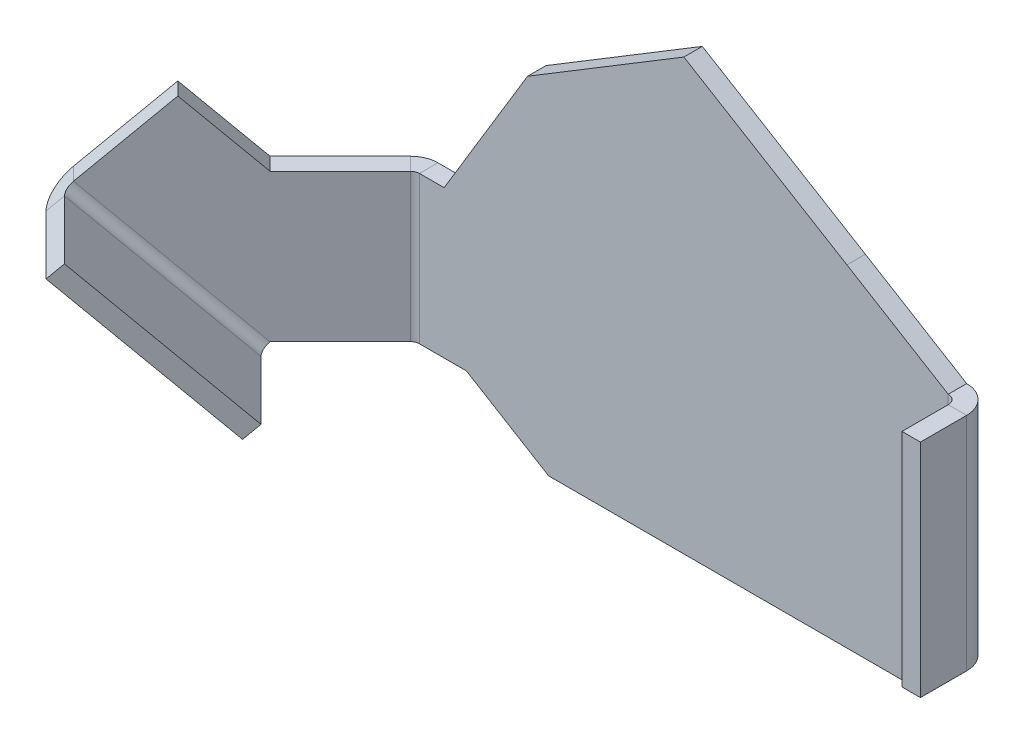
SolidWorks part; units mm, degrees
note: The reader was unsure of these and kept them because the rebuilt part matched: flange length of "Brida de arista1", "Brida de arista2", "Brida de arista3".
ref_plane "Alzado" through (0, 0, 0) normal (0, 0, 1) x (1, 0, 0)
ref_plane "Planta" through (0, 0, 0) normal (0, 1, 0) x (1, 0, 0)
ref_plane "Vista lateral" through (0, 0, 0) normal (1, 0, 0) x (0, 0, -1)
sketch "Croquis1" plane through (0, 0, 0) normal (0, 0, 1) x (1, 0, 0)
  line L1 (-21.5, -17.5) -> (21.5, -17.5)
  line L2 (-21.5, -17.5) -> (-21.5, 17.5)
  line L3 (-21.5, 17.5) -> (21.5, 17.5)
  line L4 (21.5, -17.5) -> (21.5, 17.5)
  line L5 (-21.5, -17.5) -> (21.5, 17.5) construction
  line L6 (-21.5, 17.5) -> (21.5, -17.5) construction
  point P0 (0, 0)
  dimension "D1" = 43
  dimension "D2" = 35
base flange "Brida base1" sketch "Croquis1" thickness 1.5 reverse thickness direction no parameters "D1"=0.7366
sketch "Croquis6" plane through (0, 0, 0) normal (0, 0, 1) x (1, 0, 0)
  line L0 (19.5, -17.5) -> (21.5, -13.5)
  line L1 (-21.5, -17.5) -> (21.5, -17.5) construction
  line L2 (21.5, -17.5) -> (21.5, 17.5) construction
  line L3 (19.5, -17.5) -> (-11, -17.5)
  line L4 (-21.5, -13.45) -> (-17.6841, -13.45)
  line L5 (-21.5, 17.5) -> (-21.5, -17.5) construction
  line L6 (21.5, -13.5) -> (21.5, 4.5)
  line L7 (-17.6841, -13.45) -> (-11, -17.5)
  line L8 (-21.5, -13.45) -> (-21.5, -1.45)
  line L9 (-21.5, -1.45) -> (-19.5, -1.45)
  line L10 (21.5, 4.5) -> (13.2608, 9.4923)
  line L11 (13.2608, 9.4923) -> (0, 17.5)
  line L12 (21.5, 17.5) -> (-21.5, 17.5) construction
  line L13 (-19.5, -1.45) -> (-12.7119, 9.7911)
  line L14 (-12.7119, 9.7911) -> (0, 17.5)
  line L16 (-29.7834, -22.9401) -> (29.7834, -22.9401)
  line L17 (-29.7834, -22.9401) -> (-29.7834, 22.9401)
  line L18 (-29.7834, 22.9401) -> (29.7834, 22.9401)
  line L19 (29.7834, -22.9401) -> (29.7834, 22.9401)
  line L20 (-29.7834, -22.9401) -> (29.7834, 22.9401) construction
  line L21 (-29.7834, 22.9401) -> (29.7834, -22.9401) construction
  point P12 (0, 0)
  dimension "D1" = 10.5
  dimension "D2" = 30.5
  dimension "D3" = 4
  dimension "D4" = 18
  dimension "D5" = 4.05
  dimension "D6" = 12
  dimension "D7" = 2
extrude "Cortar-Extruir1" cut sketch "Croquis6" against normal blind 10 normal cut yes
edge flange "Brida de arista1" sketch "Croquis9" flange angle 90 flange length 6 flange position bend outside bend radius 0.7366 thickness 1.5 relief rectangular parameters "D6"=10
sketch "Croquis9" plane through (21.5, 0, 0) normal (1, 0, 0) x (0, 1, 0)
  line L2 (-13.5, 0) -> (-13.5, 4.5)
  line L3 (-13.5, 4.5) -> (4.5, 4.5)
  line L4 (4.5, 4.5) -> (4.5, 0)
  line L5 (-13.5, 0) -> (4.5, 0) construction
  line L6 (-13.5, 0) -> (4.5, 0)
bend "Pliegue de arista1" bend radius 0.7366 bend angle 90 parameters "D5"=1
edge flange "Brida de arista2" sketch "Croquis12" flange angle 135 flange length 21 flange position bend outside bend radius 0.7366 thickness 1.5 relief rectangular parameters "D6"=10
sketch "Croquis12" plane through (-21.5, 0, 0) normal (-0.7071, 0, -0.7071) x (0, -1, 0)
  line L2 (1.45, 0) -> (1.45, 20.3787)
  line L3 (1.45, 20.3787) -> (13.45, 20.3787)
  line L4 (13.45, 20.3787) -> (13.45, 0)
  line L5 (1.45, 0) -> (13.45, 0) construction
  line L6 (1.45, 0) -> (13.45, 0)
bend "Pliegue de arista2" bend radius 0.7366 bend angle 45 parameters "D5"=2
sketch "Croquis13" plane through (-11.9632, 0, -11.9632) normal (-0.7071, 0, -0.7071) x (-0.7071, 0, 0.7071)
  line L0 (35.7972, -1.45) -> (21.5131, -15.7341)
  line L2 (35.7972, -13.45) -> (35.7972, -1.45) construction
  line L3 (35.7972, -1.45) -> (35.7972, -15.7341)
  line L4 (35.7972, -15.7341) -> (21.5131, -15.7341)
  dimension "D1" = 45
extrude "Cortar-Extruir2" cut sketch "Croquis13" against normal blind 10 normal cut yes
sketch "Croquis14" plane through (-11.9632, 0, -11.9632) normal (-0.7071, 0, -0.7071) x (-0.7071, 0, 0.7071)
  line L0 (23.7972, -1.45) -> (30.1612, 4.914)
  line L1 (35.7972, -1.45) -> (15.7237, -1.45) construction
  line L2 (30.1612, 4.914) -> (36.1612, -1.086)
  line L3 (35.7972, -1.45) -> (36.1612, -1.086)
  line L4 (23.7972, -1.45) -> (35.7972, -1.45)
  dimension "D1" = 135
  dimension "D2" = 12
  dimension "D3" = 9
extrude "Saliente-Extruir1" add sketch "Croquis14" against normal up to surface (1.5 mm away) up to face at (-26.9966, -7.45, 5.1915)
sketch "Croquis15" plane through (-11.9632, 0, -11.9632) normal (-0.7071, 0, -0.7071) x (-0.7071, 0, 0.7071)
  line L0 (30.1612, 4.914) -> (36.1612, -1.086)
  line L1 (36.1612, -1.086) -> (35.1005, -2.1467)
  line L2 (23.7972, -13.45) -> (36.1612, -1.086) construction
  line L3 (35.1005, -2.1467) -> (29.1005, 3.8533)
  line L4 (30.1612, 4.914) -> (23.7972, -1.45) construction
  line L5 (29.1005, 3.8533) -> (30.1612, 4.914)
  dimension "D1" = 1.5
extrude "Cortar-Extruir3" cut sketch "Croquis15" against normal blind 10 normal cut yes
edge flange "Brida de arista3" sketch "Croquis18" flange angle 90 flange length 9 flange position bend outside bend radius 0.7366 thickness 1.5 relief rectangular parameters "D6"=10
sketch "Croquis18" plane through (-24.0714, -18.6236, 2.2663) normal (-0.5, -0.7071, 0.5) x (0.5, -0.7071, -0.5)
  line L2 (-23.3019, 0) -> (-23.3019, 7.5)
  line L3 (-23.3019, 7.5) -> (-7.3166, 7.5)
  line L4 (-7.3166, 7.5) -> (-7.3166, 0)
  line L5 (-7.3166, 0) -> (-23.3019, 0) construction
  line L6 (-7.3166, 0) -> (-23.3019, 0)
bend "Pliegue de arista3" bend radius 0.7366 bend angle 90 parameters "D5"=3
sketch "Líneas de pliegue1" [suppressed] plane through (0, 0, 0) normal (0, 1, 0) x (1, 0, 0)
sketch "Cuadro delimitador1" [suppressed] plane through (0, 0, 0) normal (0, 1, 0) x (1, 0, 0)
sheet metal parameters "Chapa metálica1" thickness 1.5 parameters "D1"=0.7366
flat pattern "Chapa desplegada1" [suppressed]
sketch "Líneas de pliegue2" plane through (0, 0, 0) normal (0, 1, 0) x (1, 0, 0)
sketch3d "Cuadro delimitador2" [suppressed]
  line L0 (24, -17.5, 0) -> (-24, -17.5, 0) construction
  line L1 (24, 17.5, 0) -> (-24, 17.5, 0) construction
  line L2 (24, -17.5, 0) -> (24, 17.5, 0) construction
  line L3 (-24, -17.5, 0) -> (-24, 17.5, 0) construction
sheet metal parameters "Chapa metálica2" thickness 1.5 parameters "D1"=0.7366
flat pattern "Chapa desplegada1"
sketch "Líneas de pliegue2" plane through (0, 0, 0) normal (0, 1, 0) x (1, 0, 0)
sketch3d "Cuadro delimitador2" [suppressed]
  line L0 (-24, -17.5, 0) -> (24, -17.5, 0) construction
  line L1 (-24, 17.5, 0) -> (24, 17.5, 0) construction
  line L2 (-24, -17.5, 0) -> (-24, 17.5, 0) construction
  line L3 (24, -17.5, 0) -> (24, 17.5, 0) construction
sheet metal parameters "Chapa metálica3" thickness 1.5 parameters "D1"=0.7366
flat pattern "Chapa desplegada1"
sketch "Líneas de pliegue2" plane through (0, 0, 0) normal (0, 0, 1) x (1, 0, 0)
  line L0 (25.1676, -13.5) -> (25.1676, 4.5) construction
  line L1 (25.1676, -13.5) -> (25.1676, 4.5) construction
sketch3d "Cuadro delimitador2" [suppressed]
  line L0 (-24, -17.5, 0) -> (30.0985, -17.5, 0) construction
  line L1 (-24, 17.5, 0) -> (30.0985, 17.5, 0) construction
  line L2 (-24, -17.5, 0) -> (-24, 17.5, 0) construction
  line L3 (30.0985, -17.5, 0) -> (30.0985, 17.5, 0) construction
bend of the flat pattern "Aplanar-<Pliegue de arista1>1"
sheet metal parameters "Chapa metálica4" thickness 1.5 parameters "D1"=0.7366
flat pattern "Chapa desplegada1"
sketch "Líneas de pliegue2" plane through (0, 0, 0) normal (0, 0, 1) x (1, 0, 0)
  line L0 (23.1676, -13.5) -> (23.1676, 4.5) construction
  line L1 (23.1676, -13.5) -> (23.1676, 4.5) construction
  line L2 (-22.5838, -2) -> (-22.5838, -14) construction
  line L3 (-22.5838, -2) -> (-22.5838, -14) construction
sketch3d "Cuadro delimitador2" [suppressed]
  line L0 (-42.7411, -17.5, 0) -> (28.0985, -17.5, 0) construction
  line L1 (-42.7411, 17.5, 0) -> (28.0985, 17.5, 0) construction
  line L2 (-42.7411, -17.5, 0) -> (-42.7411, 17.5, 0) construction
  line L3 (28.0985, -17.5, 0) -> (28.0985, 17.5, 0) construction
bend of the flat pattern "Aplanar-<Pliegue de arista1>1"
bend of the flat pattern "Aplanar-<Pliegue de arista2>1"
sheet metal parameters "Chapa metálica5" thickness 1.5 parameters "D1"=0.7366
flat pattern "Chapa desplegada1"
sketch "Líneas de pliegue2" plane through (0, 0, 0) normal (0, 0, 1) x (1, 0, 0)
  line L0 (23.1676, -13.5) -> (23.1676, 4.5) construction
  line L1 (23.1676, -13.5) -> (23.1676, 4.5) construction
  line L2 (-22.5838, -1.45) -> (-22.5838, -13.45) construction
  line L3 (-22.5838, -1.45) -> (-22.5838, -13.45) construction
sketch3d "Cuadro delimitador2" [suppressed]
  line L0 (-43.2411, -17.5, 0) -> (28.0985, -17.5, 0) construction
  line L1 (-43.2411, 17.5, 0) -> (28.0985, 17.5, 0) construction
  line L2 (-43.2411, -17.5, 0) -> (-43.2411, 17.5, 0) construction
  line L3 (28.0985, -17.5, 0) -> (28.0985, 17.5, 0) construction
bend of the flat pattern "Aplanar-<Pliegue de arista1>1"
bend of the flat pattern "Aplanar-<Pliegue de arista2>1"
sheet metal parameters "Chapa metálica6" thickness 1.5 parameters "D1"=0.7366
flat pattern "Chapa desplegada1"
sketch "Líneas de pliegue2" plane through (0, 0, 0) normal (0, 0, 1) x (1, 0, 0)
  line L0 (23.1676, -13.5) -> (23.1676, 4.5) construction
  line L1 (23.1676, -13.5) -> (23.1676, 4.5) construction
  line L2 (-22.5838, -1.45) -> (-22.5838, -13.45) construction
  line L3 (-22.5838, -1.45) -> (-22.5838, -13.45) construction
sketch3d "Cuadro delimitador2" [suppressed]
  line L0 (-43.6051, -17.5, 0) -> (28.0985, -17.5, 0) construction
  line L1 (-43.6051, 17.5, 0) -> (28.0985, 17.5, 0) construction
  line L2 (-43.6051, -17.5, 0) -> (-43.6051, 17.5, 0) construction
  line L3 (28.0985, -17.5, 0) -> (28.0985, 17.5, 0) construction
bend of the flat pattern "Aplanar-<Pliegue de arista1>1"
bend of the flat pattern "Aplanar-<Pliegue de arista2>1"
sheet metal parameters "Chapa metálica7" thickness 1.5 parameters "D1"=0.7366
flat pattern "Chapa desplegada1"
sketch "Líneas de pliegue2" plane through (0, 0, 0) normal (0, 0, 1) x (1, 0, 0)
  line L0 (23.1676, -13.5) -> (23.1676, 4.5) construction
  line L1 (23.1676, -13.5) -> (23.1676, 4.5) construction
  line L2 (-22.5838, -1.45) -> (-22.5838, -13.45) construction
  line L3 (-22.5838, -1.45) -> (-22.5838, -13.45) construction
sketch3d "Cuadro delimitador2" [suppressed]
  line L0 (-42.5444, -17.5, 0) -> (28.0985, -17.5, 0) construction
  line L1 (-42.5444, 17.5, 0) -> (28.0985, 17.5, 0) construction
  line L2 (-42.5444, -17.5, 0) -> (-42.5444, 17.5, 0) construction
  line L3 (28.0985, -17.5, 0) -> (28.0985, 17.5, 0) construction
bend of the flat pattern "Aplanar-<Pliegue de arista1>1"
bend of the flat pattern "Aplanar-<Pliegue de arista2>1"
sheet metal parameters "Chapa metálica8" thickness 1.5 parameters "D1"=0.7366
flat pattern "Chapa desplegada1"
sketch "Líneas de pliegue2" plane through (0, 0, 0) normal (0, 0, 1) x (1, 0, 0)
  line L0 (22.6676, -13.5) -> (22.6676, 4.5) construction
  line L1 (22.6676, -13.5) -> (22.6676, 4.5) construction
  line L2 (-22.0838, -1.45) -> (-22.0838, -13.45) construction
  line L3 (-22.0838, -1.45) -> (-22.0838, -13.45) construction
  line L4 (-42.87, -2.9723) -> (-31.5667, -14.2756) construction
  line L5 (-42.87, -2.9723) -> (-31.5667, -14.2756) construction
sketch3d "Cuadro delimitador2" [suppressed]
  line L0 (-47.9836, -20.3382, 0) -> (28.5079, -17.1211, 0) construction
  line L1 (-49.4874, 15.4186, 0) -> (27.004, 18.6357, 0) construction
  line L2 (-47.9836, -20.3382, 0) -> (-49.4874, 15.4186, 0) construction
  line L3 (28.5079, -17.1211, 0) -> (27.004, 18.6357, 0) construction
bend of the flat pattern "Aplanar-<Pliegue de arista1>1"
bend of the flat pattern "Aplanar-<Pliegue de arista2>1"
bend of the flat pattern "Aplanar-<Pliegue de arista3>1"
